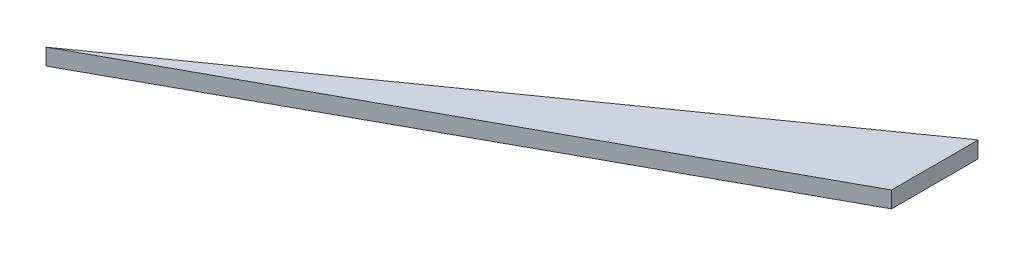
SolidWorks part; units mm, degrees
ref_plane "Front Plane" through (0, 0, 0) normal (0, 0, 1) x (1, 0, 0)
ref_plane "Top Plane" through (0, 0, 0) normal (0, 1, 0) x (1, 0, 0)
ref_plane "Right Plane" through (0, 0, 0) normal (1, 0, 0) x (0, 0, -1)
sketch "Sketch1" plane through (0, 0, 0) normal (0, 1, 0) x (1, 0, 0)
  line L1 (0, 0) -> (263.3435, 0)
  line L2 (0, 0) -> (0, 204.1914)
  line L3 (0, 204.1914) -> (263.3435, 204.1914)
  line L4 (263.3435, 0) -> (263.3435, 204.1914)
  line L5 (0, 0) -> (263.3435, 204.1914) construction
  line L6 (0, 204.1914) -> (263.3435, 0) construction
  point P4 (131.6717, 102.0957)
  dimension "D1" = 263.3435
  dimension "D2" = 204.1914
extrude "Boss-Extrude1" add sketch "Sketch1" along normal blind 4.6
sketch "Sketch3" plane through (0, 0, 0) normal (0, -1, 0) x (1, 0, 0)
  line L14 (263.3435, -127.7494) -> (192.1234, -199.5914)
  line L15 (192.1234, -199.5914) -> (195.3479, -202.8441)
  line L16 (195.3479, -202.8441) -> (266.568, -131.002)
  line L17 (266.568, -131.002) -> (263.3435, -127.7494)
  line L18 (109.3951, 51.8558) -> (263.4085, -103.5027)
  line L19 (263.4085, -103.5027) -> (266.6331, -100.25)
  line L20 (266.6331, -100.25) -> (112.6196, 55.1085)
  line L21 (112.6196, 55.1085) -> (109.3951, 51.8558)
  line L22 (267.9037, -127.821) -> (267.9037, -103.437)
  line L23 (267.9037, -103.437) -> (263.3435, -103.437)
  line L24 (263.3435, -103.437) -> (263.3435, -127.821)
  line L25 (263.3435, -127.821) -> (267.9037, -127.821)
  line L26 (81.5889, 8.9697) -> (109.6283, -19.3145)
  line L27 (109.6283, -19.3145) -> (81.3786, -47.8109)
  line L28 (263.3435, -103.437) -> (109.6283, -19.3145)
  line L29 (109.6283, -19.3145) -> (263.3435, -127.821)
  line M7 (263.3435, -204.1914) -> (263.3435, 0)
extrude "Cut-Extrude2" cut sketch "Sketch3" against normal through all flip side to cut contours L28 L29 L14 M7 region at (212.1051, 0, -83.5242)
equation "\"MDF\"= 4.8mm"
equation "\"Foamcore\"= 4.6mm"
equation "\"GMaterial\"= \"MDF\""
equation "\"PCB\" = 1.6mm"
equation "\"BaseWidth\" = 10in"
equation "\"SkidLength\" = 1in"
equation "\"SkidClearance\" = 0.4in"
equation "\"MotorMountLength\" = 2in"
equation "\"MotorMountWidth\" = \"GMaterial\""
equation "\"MotorMountHeight\" = 2.25in"
equation "\"UnoStackWidth\" = 77.4mm"
equation "\"UnoStackLength\" = 79.8mm"
equation "\"UnoStackHeight\" = 34.2mm"
equation "\"TallHexRiserHeight\" = 22.2mm"
equation "\"PingPongBallSize\" = 40mm"
equation "\"BarrelLength\" = 9in"
equation "\"BarrelSize\" = \"PingPongBallSize\""
equation "\"PlatformLength\" = 4in"
equation "\"PlatformWidth\" = 6in"
equation "\"WheelDiameter\"=2.99213"
equation "\"ServoMountHeight\"=2.49223"
equation "\"ServoGearHeight\" = 0.95330261in"
equation "\"ServoMountLength\"= 1.53774"
equation "\"PivotHoleRadius\"= 0.616358"
equation "\"PlatformMountHeight\" = 3.19"
equation "\"TensionOffSet\"= .3mm"
equation "\"MotorMountWedge\"=0.333333"
equation "\"LaserCutterOffset\"= .3mm"
equation "\"BumperWidth\"=11"
equation "\"PitcherWheelCompression\" = 2.5mm"
equation "\"BarrelToHopperDistance\" = 0.5405in"
equation "\"PitchingWheelWidth\" = 26.2mm"
equation "\"PitchingWheelDiameter\" = 65.5mm"
equation "\"PitchingWheelMountOffset\" = 8.4mm"
equation "\"PitchingWheelInnerDiameter\" = 45.5mm"
equation "\"PitchingWheelBoltShoulder\" = 4.5mm"
equation "\"BrassCouplingLength\" = 18mm"
equation "\"PitchingMotorHeight\" = 57.0mm"
equation "\"PitchingMotorShaftTopHeight\" = \"PitchingMotorHeight\" - 44.1mm"
equation "\"PitchingMotorBodyHeight\" = 38mm"
equation "\"PitchingMotorTopShoulderHeight\" = 40.6mm - \"PitchingMotorBodyHeight\" "
equation "\"PitchingMotorBottomShoulderHeight\" = 40.2mm - \"PitchingMotorBodyHeight\""
equation "\"PitchingMotorBottomShaftHeight\" = \"PitchingMotorHeight\" - \"PitchingMotorShaftTopHeight\" - \"PitchingMotorTopShoulderHeight\" - \"PitchingMotorBodyHeight\" - \"PitchingMotorBottomShoulderHeight\""
equation "\"PitchingMotorShaftDiameter\" = 2.2mm"
equation "\"PitchingMotorBodyDiameter\" = 27.4mm"
equation "\"PitchingMotorTopShoulderDiameter\" = 9.8mm"
equation "\"PitchingMotorBottomShoulderDiameter\" = 9.8mm"
equation "\"BrassCouplingHexSize\" = 12mm"
equation "\"BrassCouplingBoreSize\" = 3.17mm"
equation "\"PitchingMotorMountingHoleDistance\" = 16mm"
equation "\"Acrylic\" = 4.4mm"
equation "\"PitchingMotorDistance\" = \"PitchingWheelDiameter\" + \"PingPongBallSize\" - \"PitcherWheelCompression\"*2"
equation "\"PitchingMotorPlatformOffset\"=1"
equation "\"ServoPlatformOffset\"=1.64173"
equation "\"BallBearingDiameter\" = 22mm"
equation "\"BallBearingWidth\" = 9mm"
equation "\"BallBearingHexShoulder\" = 9mm - 5.9mm"
equation "\"BallBearingHexSize\" = .36in"
equation "\"PlatformMountFootLength\"=0.857143"
equation "\"WheelWidth\"= 26mm"
equation "\"ServoMountReductionBackHeight\"=2.25"
equation "\"PlatformBottomWidthThird\" =  0.857143in"
equation "\"PlatformMountBackReductionHeight\"= 2.5in"
equation "\"PlatformMountBackReductionWidth\"= 3/7in"
equation "\"PlatformMountFrontReductionWidth\" =  1.46226in"
equation "\"PlatformMountFrontReductionHeight\" = 2.5in"
equation "\"HopperLongWallLength\" = 8.646in"
equation "\"HopperShortWallLength\" = 0.9571in"
equation "\"HopperHeight\" = 3.50in - \"Foamcore\""
equation "\"HoperLongSlantLength\" = 7.064in"
equation "\"HopperBottomTemplateWidth\" = 8.03903165in"
equation "\"HopperBottomTemplateLength\" = 10.367854in"
equation "\"D1@Sketch1\"=\"HopperBottomTemplateLength\""
equation "\"D2@Sketch1\"=\"HopperBottomTemplateWidth\""
equation "\"D1@Boss-Extrude1\"=\"Foamcore\""
